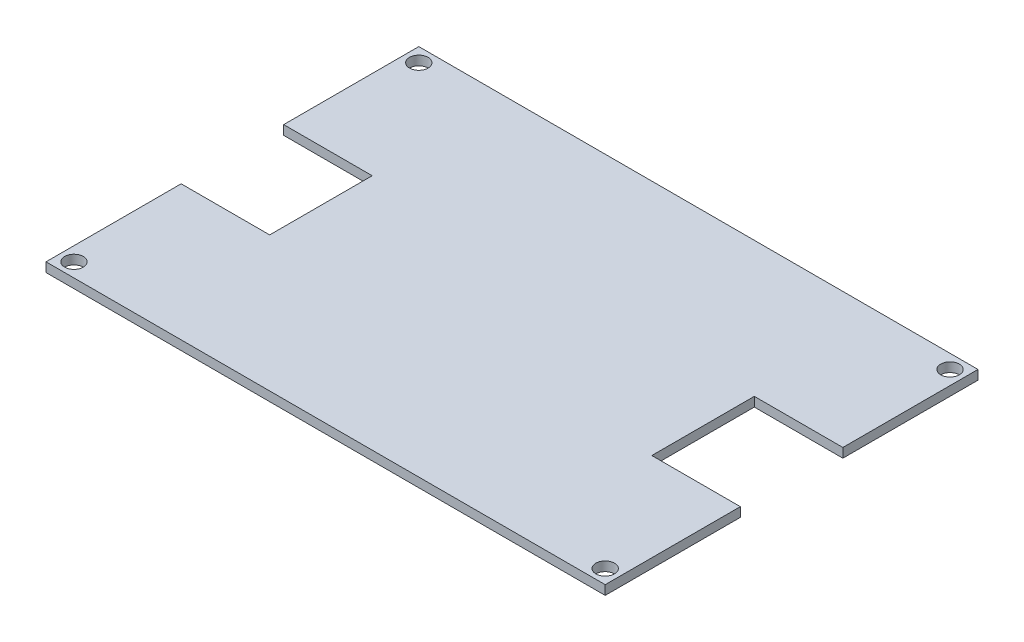
SolidWorks part; units mm, degrees
ref_plane "Front Plane" through (0, 0, 0) normal (0, 0, 1) x (1, 0, 0)
ref_plane "Top Plane" through (0, 0, 0) normal (0, 1, 0) x (1, 0, 0)
ref_plane "Right Plane" through (0, 0, 0) normal (1, 0, 0) x (0, 0, -1)
sketch "Sketch1" plane through (0, 0, 0) normal (0, 1, 0) x (1, 0, 0)
  line L1 (-60, -40) -> (60, -40)
  line L2 (-60, -40) -> (-60, 40)
  line L3 (-60, 40) -> (60, 40)
  line L4 (60, -40) -> (60, 40)
  line L5 (-60, -40) -> (60, 40) construction
  line L6 (-60, 40) -> (60, -40) construction
  point P0 (0, 0)
  dimension "D1" = 120
  dimension "D2" = 80
extrude "Boss-Extrude1" add sketch "Sketch1" along normal blind 2
sketch "Sketch2" plane through (0, 2, 0) normal (0, 1, 0) x (1, 0, 0)
  line L0 (-60, 11) -> (-60, -11)
  line L1 (-60, 40) -> (-60, -40) construction
  line L2 (-60, 11) -> (-41, 11)
  line L3 (-41, 11) -> (-41, -11)
  line L4 (-41, -11) -> (-60, -11)
  line L9 (41, -11) -> (60, -11)
  line L10 (41, 11) -> (41, -11)
  line L11 (60, 11) -> (41, 11)
  dimension "D3" = 19
extrude "Cut-Extrude1" cut sketch "Sketch2" against normal blind 20 and the other way blind 20 contours L0 L4 L3 L2
sketch "Sketch3" plane through (0, 2, 0) normal (0, 1, 0) x (1, 0, 0)
  line L0 (0, 0) -> (0, -40) construction
  line L1 (-60, -40) -> (60, -40) construction
  line L2 (41, 11) -> (60, 11)
  line L3 (60, -40) -> (60, 40) construction
  line L4 (60, 11) -> (60, -11)
  line L5 (41, 11) -> (41, -11)
  line L7 (41, -11) -> (60, -11)
  dimension "D1" = 19
extrude "Cut-Extrude2" cut sketch "Sketch3" against normal blind 20 and the other way blind 20
sketch "Sketch4" plane through (0, 2, 0) normal (0, 1, 0) x (1, 0, 0)
  circle A0 centre (-57, 37) radius 2
  circle A1 centre (57, 37) radius 2
  circle A2 centre (57, -37) radius 2
  circle A3 centre (-57, -37) radius 2
  point P0 (0, 0)
extrude "Cut-Extrude3" cut sketch "Sketch4" against normal blind 20 and the other way blind 20
